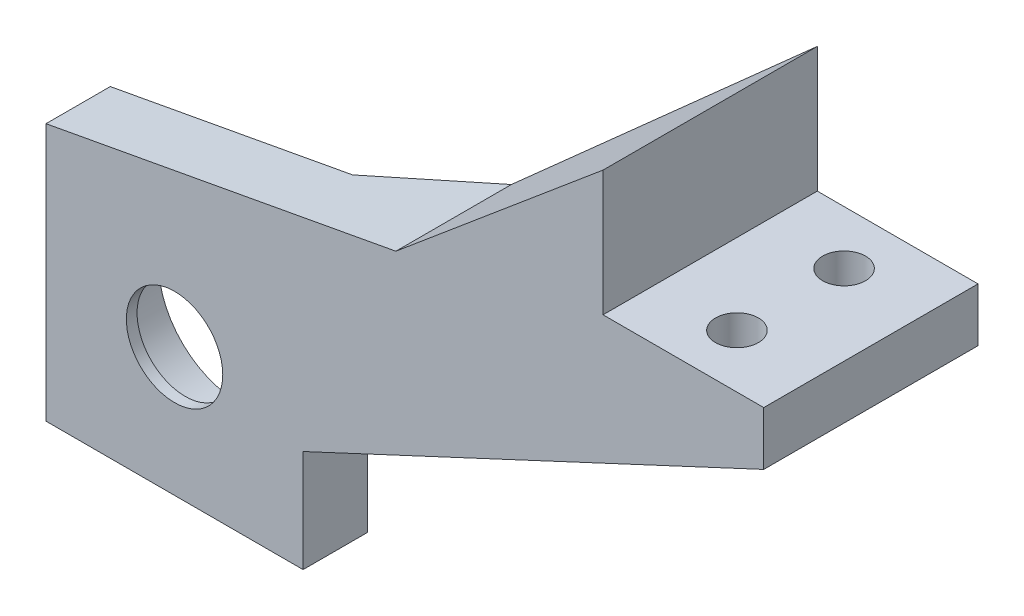
SolidWorks part; units mm, degrees
material "ABS"
ref_plane "Front Plane" through (0, 0, 0) normal (0, 0, 1) x (1, 0, 0)
ref_plane "Top Plane" through (0, 0, 0) normal (0, 1, 0) x (1, 0, 0)
ref_plane "Right Plane" through (0, 0, 0) normal (1, 0, 0) x (0, 0, -1)
sketch "Sketch1" plane through (0, 0, 0) normal (0, 0, 1) x (1, 0, 0)
  circle A0 centre (0, 0) radius 7.5
  circle A1 centre (0, 0) radius 4.5
  circle A2 centre (0, 0) radius 10
  dimension "D1" = 15
  dimension "D2" = 20
  dimension "D3" = 9
extrude "Boss-Extrude1" add sketch "Sketch1" against normal up to surface (5 mm away) contours A2 A0 region at (-9.7172, 0, 0)
extrude "Boss-Extrude2" add sketch "Sketch1<3>" along normal blind 1 contours A0 A1 | A2 A0 region at (-7.2879, 0, 0) region at (-9.7172, 0, 0)
sketch "Sketch1<3>" plane through (0, 0, 0) normal (0, 0, 1) x (1, 0, 0) same geometry as "Sketch1"
sketch "Sketch2" plane through (0, 0, 1) normal (0, 0, 1) x (1, 0, 0)
  line L3 (55, 22.6) -> (40, 22.6)
  line L5 (-12, -0.9326) -> (-12, -12)
  line L6 (-12, -12) -> (12, -12)
  line L8 (40, 22.6) -> (40, 17.6)
  line L13 (40, 17.6) -> (55, 17.6)
  line L14 (55, 17.6) -> (55, 22.6)
  line L15 (-86, 22.6) -> (266, 22.6) construction
  line L16 (10.6203, 22.6) -> (-12, 12.052)
  line L17 (-12, -0.9326) -> (-12, 12.052)
  line L18 (40, 22.6) -> (10.6203, 22.6)
  line L19 (55, 17.6) -> (12, -2.4512)
  line L20 (12, -2.4512) -> (12, -12)
  line L21 (10.6203, 22.6) -> (40, 36.3)
  line L23 (34.0705, 37.9485) -> (-8.8692, 17.9254) construction
  line L24 (40, 22.6) -> (40, 34.3) construction
  line L25 (40, 36.3) -> (40, 22.6)
  circle A1 centre (0, 0) radius 10
  circle A2 centre (0, 0) radius 10 construction
  circle M4 centre (0, 0) radius 10
  dimension "D1" = 12
  dimension "D2" = 24
  dimension "D3" = 15
  dimension "D4" = 5
  dimension "D5" = 25
  dimension "D6" = 4
  dimension "D7" = 12
  dimension "D8" = 2
  dimension "D9" = 0
extrude "Boss-Extrude3" add sketch "Sketch2" against normal up to surface (6 mm away) contours L8 M4 | L6 L5 M4 | L8 | L25 L21 L18 region at (47.5, 20.1, 1) region at (16.0369, 9.9628, 1) region at (30.2068, 27.1667, 1) up to face at (-10, 0, -5)
sketch "Sketch3" plane through (0, 22.6, 0) normal (0, -1, 0) x (1, 0, 0)
  line L0 (40, -286) -> (40, 14) construction
  line L1 (55, -5) -> (40, -5)
  line L2 (55, -5) -> (55, -19)
  line L3 (55, -19) -> (40, -19)
  line L4 (40, -5) -> (40, -19)
  line L5 (55, -5) -> (40, -19) construction
  line L6 (55, -19) -> (40, -5) construction
  line L7 (55, 1) -> (12, 1) construction
  line L8 (40, -19) -> (10.6203, -5)
  line L9 (55, -5) -> (55, 1) construction
  line L10 (40, -5) -> (10.6203, -5)
  line L11 (40, -5) -> (-12, -5) construction
  point P4 (47.5, -12)
  dimension "D1" = 20
  dimension "D2" = 29.3797
extrude "Boss-Extrude7" add sketch "Sketch3" along normal up to surface (11.9946 mm away) contours L4 L10 L8 | L1 L4 L3 L2 region at (47.5, 22.6, -12) region at (30.2068, 22.6, -9.6667) up to face at (33.5, 7.5744, -2)
sketch "Sketch4" plane through (0, 22.6, 0) normal (0, -1, 0) x (1, 0, 0)
  line L1 (55, 1) -> (40, 1)
  line L2 (55, 1) -> (55, -19)
  line L3 (55, -19) -> (40, -19)
  line L4 (40, 1) -> (40, -19)
  line L5 (55, 1) -> (40, -19) construction
  line L6 (55, -19) -> (40, 1) construction
  line L7 (55, -19) -> (55, 1) construction
  line L8 (55, -9) -> (40, -9) construction
  line L9 (47.5, -9.8431) -> (43.9, -11.9215)
  line L10 (43.9, -11.9215) -> (43.9, -16.0785)
  line L11 (43.9, -16.0785) -> (47.5, -18.1569)
  line L12 (47.5, -18.1569) -> (51.1, -16.0785)
  line L13 (51.1, -16.0785) -> (51.1, -11.9215)
  line L14 (51.1, -11.9215) -> (47.5, -9.8431)
  line L21 (51.1, -6.0785) -> (47.5, -8.1569)
  line L22 (51.1, -1.9215) -> (51.1, -6.0785)
  line L23 (47.5, 0.1569) -> (51.1, -1.9215)
  line L24 (43.9, -1.9215) -> (47.5, 0.1569)
  line L25 (43.9, -6.0785) -> (43.9, -1.9215)
  line L26 (47.5, -8.1569) -> (43.9, -6.0785)
  line L27 (55, 1) -> (40, 1) construction
  circle A0 centre (47.5, -14) radius 3.6 construction
  circle A1 centre (47.5, -4) radius 3.6 construction
  circle A2 centre (47.5, -14) radius 2
  circle A3 centre (47.5, -4) radius 2
  point P4 (47.5, -9)
  point P28 (45.7, -10.8823)
  dimension "D3" = 4
  dimension "D1" = 7.5
  dimension "D2" = 7.2
  dimension "D4" = 5
  dimension "D5" = 15
  dimension "D6" = 20
extrude "Cut-Extrude4" cut sketch "Sketch4" along normal through all contours A2 | A3 region at (47.5, 22.6, -14) region at (47.5, 22.6, -4)
extrude "Cut-Extrude5" cut sketch "Sketch4<3>" along normal through all from offset 3 contours L26 L21 L22 L23 L24 L25 A3 | L13 L14 L9 L10 L11 L12 A2 region at (49.245, 22.6, -10.9776) region at (49.245, 22.6, -7.0224)
sketch "Sketch4<3>" plane through (0, 22.6, 0) normal (0, -1, 0) x (1, 0, 0) same geometry as "Sketch4"
extrude "Boss-Extrude8" add sketch "Sketch3<4>" against normal up to surface (13.7 mm away) contours L4 L10 L8 region at (30.2068, 22.6, -9.6667) up to face at (13.3241, 23.8608, -2.6)
sketch "Sketch3<4>" plane through (0, 22.6, 0) normal (0, -1, 0) x (1, 0, 0) same geometry as "Sketch3"
sketch "Sketch6" plane through (0, 0, 1) normal (0, 0, 1) x (1, 0, 0)
  line L0 (20.6588, 18.0708) -> (40, 34.3)
  line L1 (20.6588, 18.0708) -> (87.2578, 73.954) construction
  line L2 (40, 36.3) -> (40, 22.6) construction
  line L3 (20.6588, 18.0708) -> (15.104, 24.6908)
  line L4 (40, 36.3) -> (-12, 12.052) construction
  line L5 (18.5376, 20.5988) -> (20.6588, 18.0708) construction
  line L6 (-12, 12.052) -> (20.6588, 18.0708)
  line L7 (-12, 12.052) -> (40, 36.3)
  line L8 (40, 36.3) -> (40, 34.3)
  line M7 (40, 22.6) -> (40, 36.3)
  line M8 (40, 36.3) -> (-12, 12.052)
extrude "Cut-Extrude6" cut sketch "Sketch6" against normal through all contours L6 L3 M8 | L3 L0 M7 M8 region at (26.4522, 26.8162, 1) region at (7.9209, 18.2712, 1)
